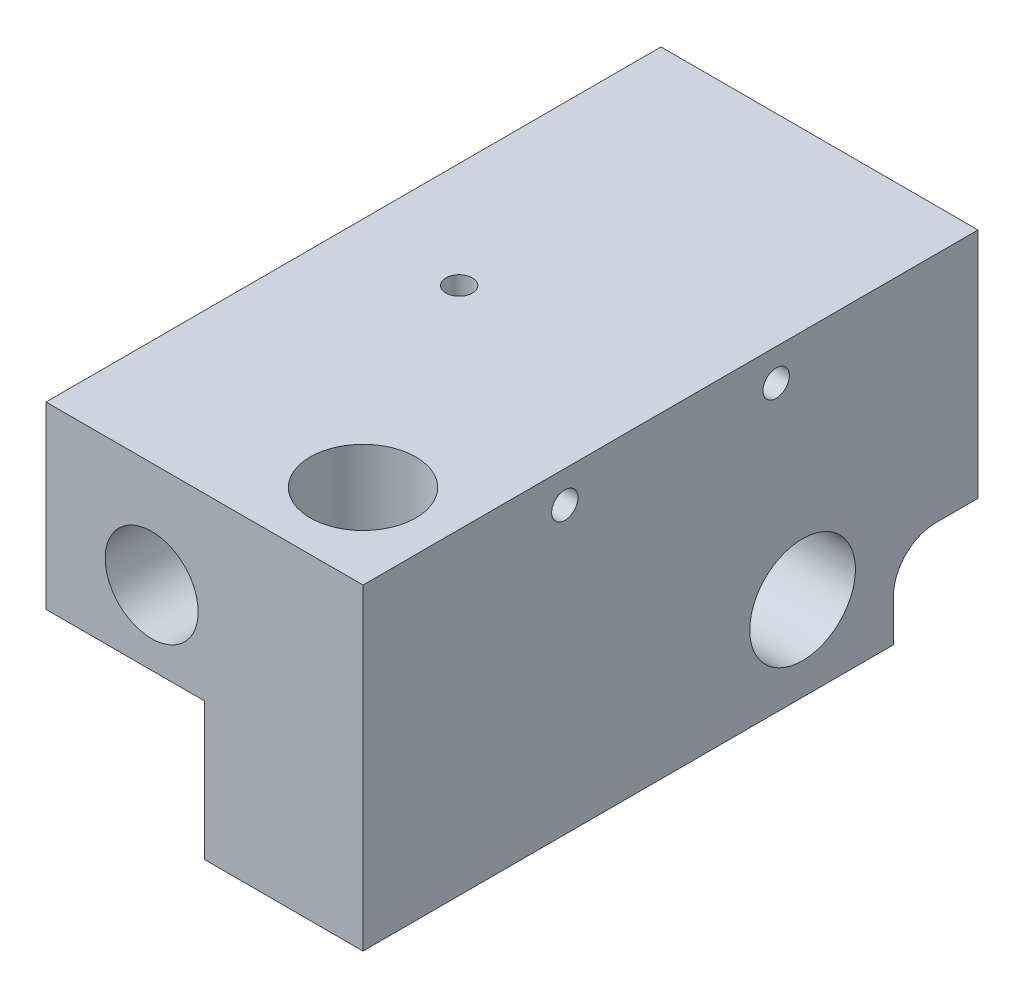
SolidWorks part; units mm, degrees
material "6061-T4 (SS)"
ref_plane "Piano frontale" through (0, 0, 0) normal (0, 0, 1) x (1, 0, 0)
ref_plane "Piano superiore" through (0, 0, 0) normal (0, 1, 0) x (1, 0, 0)
ref_plane "Piano destro" through (0, 0, 0) normal (1, 0, 0) x (0, 0, -1)
sketch "Schizzo1" plane through (0, 0, 0) normal (0, 0, 1) x (1, 0, 0)
  line L1 (0, 0) -> (30, 0)
  line L2 (0, 0) -> (0, 30)
  line L3 (0, 30) -> (30, 30)
  line L4 (30, 0) -> (30, 30)
  dimension "D1" = 30
extrude "Estrusione-Estrusione1" add sketch "Schizzo1" along normal blind 58.2
sketch "Schizzo2" plane through (0, 0, 0) normal (0, -1, 0) x (1, 0, 0)
  line L1 (0, 58.2) -> (30, 58.2) construction
  line L3 (30, 58.2) -> (30, 0) construction
  circle A0 centre (22, 50.2) radius 5
  dimension "D1" = 10
  dimension "D3" = 3
  dimension "D2" = 3
extrude "Taglio-Estrusione1" cut sketch "Schizzo2" against normal up to next
ref_point "Punto1"
sketch "Schizzo3" plane through (0, 0, 0) normal (-1, 0, 0) x (0, 0, 1)
  line L0 (50.2, 0) -> (50.2, 8) construction
  line L1 (50.2, 8) -> (16.6, 8) construction
  line L3 (58.2, 0) -> (0, 0) construction
  circle A0 centre (16.6, 8) radius 5
  dimension "D1" = 10
  dimension "D3" = 3
  dimension "D2" = 33.6
extrude "Taglio-Estrusione2" cut sketch "Schizzo3" against normal up to next
sketch "Schizzo5" plane through (0, 0, 0) normal (0, 0, -1) x (-1, 0, 0)
  line L0 (0, 30) -> (-30, 0) construction
  line L1 (0, 30) -> (0, 0) construction
  line L2 (-30, 30) -> (0, 30) construction
  circle A0 centre (-10, 20) radius 6
  dimension "D1" = 12
  dimension "D2" = 10
  dimension "D3" = 10
hole_wizard "Foro filettato G1/8-1" positions "Schizzo3D1" profile "Schizzo8" tap size "G1/8" standard "BSI"
sketch3d "Schizzo3D1"
  line L1 (30, 30, 58.2) -> (0, 30, 58.2) construction
  line L2 (0, 30, 58.2) -> (0, 0, 58.2) construction
  point P0 (10, 20, 58.2)
  dimension "D1" = 10
  dimension "D2" = 10
sketch "Schizzo8" plane through (10, 20, 58.2) normal (1, 0, 0) x (0, -1, 0)
  line L0 (0, 0) -> (0, 12.6438)
  line L1 (0, 12.6438) -> (4.4, 10)
  line L2 (4.4, 10) -> (4.4, 0)
  line L5 (4.4, 0) -> (0, 0)
  line L10 (0, 12.6438) -> (-4.4, 10) construction
  line L11 (0, -6.35) -> (0, 107.95) construction
  dimension "Tap Drill Dia." = 8.8
  dimension "Tap Drill Depth" = 10
  dimension "Drill Angle" = 118
sketch "Schizzo20" plane through (0, 0, 0) normal (-1, 0, 0) x (0, 0, 1)
  line L0 (4, 8) -> (0, 8)
  line L1 (0, 0) -> (8, 0) construction
  line L2 (0, 0) -> (0, 8) construction
  line L3 (0, 8) -> (8, 8) construction
  line L4 (8, 0) -> (8, 8) construction
  line L5 (0, 8) -> (0, 0)
  line L6 (0, 0) -> (8, 0)
  line L7 (8, 0) -> (8, 4)
  arc A1 (8, 4) -> (4, 8) centre (4, 4) ccw
  dimension "D1" = 8
  dimension "D2" = 8
  dimension "D3" = 8
extrude "Taglio-Estrusione5" cut sketch "Schizzo20" against normal blind 10
sketch "Schizzo21" plane through (30, 0, 0) normal (1, 0, 0) x (0, 0, -1)
  line L0 (-8, 0) -> (-8, 4) construction
  line L2 (-4, 8) -> (0, 8) construction
  line L3 (0, 8) -> (0, 0) construction
  line L4 (-8, 0) -> (-8, 4)
  line L5 (0, 0) -> (-8, 0)
  line L6 (-4, 8) -> (0, 8)
  line L7 (0, 8) -> (0, 0)
  arc A0 (-4, 8) -> (-8, 4) centre (-4, 4) ccw construction
  arc A1 (-4, 8) -> (-8, 4) centre (-4, 4) ccw
extrude "Taglio-Estrusione6" cut sketch "Schizzo21" against normal blind 10
sketch "Schizzo23" plane through (10, 0, 0) normal (-1, 0, 0) x (0, 0, 1)
  circle A0 centre (3.6, 3.6) radius 1.6
extrude "Taglio-Estrusione7" cut sketch "Schizzo23" against normal up to surface (10 mm away) up to face at (20, 4.1657, 4.1657)
sketch "Schizzo25" plane through (30, 0, 0) normal (1, 0, 0) x (0, 0, -1)
  point P0 (-39.1, 27)
  point P1 (-19.1, 27)
hole_wizard "Foro filettato M3-2" positions "Schizzo3D2" profile "Schizzo27" tap size "M3" standard "ISO"
sketch3d "Schizzo3D2"
  point P0 (30, 27, 39.1)
  point P3 (30, 27, 19.1)
sketch "Schizzo27" plane through (30, 27, 39.1) normal (0, 1, 0) x (0, 0, -1)
  line L0 (0, 0) -> (0, 12.2511)
  line L1 (0, 12.2511) -> (1.25, 11.5)
  line L2 (1.25, 11.5) -> (1.25, 0)
  line L5 (1.25, 0) -> (0, 0)
  line L10 (0, 12.2511) -> (-1.25, 11.5) construction
  line L11 (0, -6.35) -> (0, 107.95) construction
  dimension "Tap Drill Dia." = 2.5
  dimension "Tap Drill Depth" = 11.5
  dimension "Drill Angle" = 118
cosmetic thread "Filettatura del foro2" parameters "D1"=10, "D2"=3
cosmetic thread "Filettatura del foro3" parameters "D1"=10, "D2"=3
extrude "Taglio-Estrusione8" cut sketch "Schizzo5" against normal blind 13
sketch "Schizzo28" plane through (0, 0, 13) normal (0, 0, -1) x (-1, 0, 0)
  circle A0 centre (-10, 20) radius 3
  dimension "D1" = 6
extrude "Taglio-Estrusione9" cut sketch "Schizzo28" against normal through all
sketch "Schizzo29" plane through (0, 0, 0) normal (-1, 0, 0) x (0, 0, 1)
  line L0 (20.2683, 0) -> (58.2, 0)
  line L1 (58.2, 0) -> (58.2, 13)
  line L2 (58.2, 13) -> (58.2, 0)
  line L5 (58.2, 0) -> (58.2, 30) construction
  line L7 (58.2, 0) -> (8, 0) construction
  line L8 (42.2, 13) -> (58.2, 13)
  arc A1 (42.2, 13) -> (20.2683, 0) centre (42.2, -12) ccw
  line M6 (8, 0) -> (58.2, 0)
  line M7 (58.2, 0) -> (58.2, 30)
  dimension "D3" = 25
  dimension "D1" = 16
  dimension "D2" = 12
extrude "Taglio-Estrusione11" cut sketch "Schizzo29" against normal blind 15 contours L8 A1 M6 M7 region at (0, 5.9257, 41.9996)
sketch "Schizzo30" plane through (0, 30, 0) normal (0, 1, 0) x (1, 0, 0)
  line L0 (10, 0) -> (10, -58.2) construction
  line L1 (30, 0) -> (0, 0) construction
  line L3 (0, -29.1) -> (30, -29.1) construction
  line L4 (0, -58.2) -> (0, 0) construction
  line L5 (30, -58.2) -> (0, -58.2) construction
  point P4 (10, -29.1)
hole_wizard "Foro filettato M3-3" positions "Schizzo3D4" profile "Schizzo31" tap size "M3" standard "DIN"
sketch3d "Schizzo3D4"
  point P0 (10, 30, 29.1)
  point P2 (10, 30, 29.1)
  point P4 (10, 30, 29.1)
  point P7 (10, 30, 29.1)
  point P9 (10, 30, 29.1)
sketch "Schizzo31" plane through (10, 30, 29.1) normal (1, 0, 0) x (0, 0, 1)
  line L0 (0, 0) -> (0, 5.7511)
  line L1 (0, 5.7511) -> (1.25, 5)
  line L2 (1.25, 5) -> (1.25, 0)
  line L5 (1.25, 0) -> (0, 0)
  line L10 (0, 5.7511) -> (-1.25, 5) construction
  line L11 (0, -6.35) -> (0, 107.95) construction
  dimension "Tap Drill Dia." = 2.5
  dimension "Tap Drill Depth" = 5
  dimension "Drill Angle" = 118
